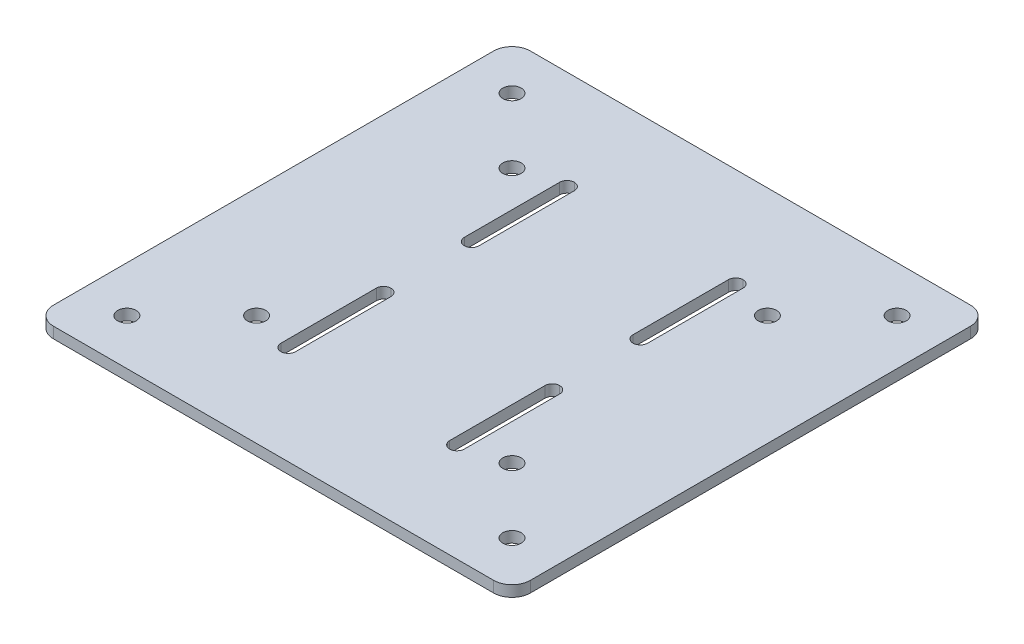
SolidWorks part; units mm, degrees
ref_plane "Front Plane" through (0, 0, 0) normal (0, 0, 1) x (1, 0, 0)
ref_plane "Top Plane" through (0, 0, 0) normal (0, 1, 0) x (1, 0, 0)
ref_plane "Right Plane" through (0, 0, 0) normal (1, 0, 0) x (0, 0, -1)
sketch "Sketch1" plane through (0, 0, 0) normal (0, 1, 0) x (1, 0, 0)
  line L0 (-52.5, 52.5) -> (52.5, 52.5) construction
  line L1 (-65, 65) -> (65, 65)
  line L2 (-65, 65) -> (-65, -65)
  line L3 (-65, -65) -> (65, -65)
  line L4 (65, 65) -> (65, -65)
  line L5 (-65, 65) -> (65, -65) construction
  line L6 (-65, -65) -> (65, 65) construction
  line L7 (-99.0677, 0) -> (99.0677, 0) construction
  line L9 (-25, 40) -> (-21, 40)
  line L10 (-25, 40) -> (25, 40) construction
  line L11 (-25, 40) -> (-25, -40) construction
  line L12 (-25, -40) -> (25, -40) construction
  line L13 (25, 40) -> (25, -40) construction
  line L14 (-25, 40) -> (25, -40) construction
  line L15 (-25, -40) -> (25, 40) construction
  line L16 (-25, 40) -> (-25, 10)
  line L17 (-25, 10) -> (-21, 10)
  line L18 (-21, 40) -> (-21, 10)
  line L19 (-25, 40) -> (-21, 10) construction
  line L20 (-25, 10) -> (-21, 40) construction
  line L21 (25, 40) -> (21, 40)
  line L22 (25, 40) -> (25, 10)
  line L23 (25, 10) -> (21, 10)
  line L24 (21, 40) -> (21, 10)
  line L25 (25, 40) -> (21, 10) construction
  line L26 (25, 10) -> (21, 40) construction
  line L27 (25, -40) -> (21, -40)
  line L28 (25, -40) -> (25, -10)
  line L29 (25, -10) -> (21, -10)
  line L30 (21, -40) -> (21, -10)
  line L31 (25, -40) -> (21, -10) construction
  line L32 (25, -10) -> (21, -40) construction
  line L33 (-25, -40) -> (-21, -40)
  line L34 (-25, -40) -> (-25, -10)
  line L35 (-25, -10) -> (-21, -10)
  line L36 (-21, -40) -> (-21, -10)
  line L37 (-25, -40) -> (-21, -10) construction
  line L38 (-25, -10) -> (-21, -40) construction
  circle A0 centre (-52.5, 52.5) radius 2.5
  circle A1 centre (-34.8223, 34.8223) radius 2.5
  circle A2 centre (52.5, 52.5) radius 2.5
  circle A3 centre (34.8223, 34.8223) radius 2.5
  circle A4 centre (52.5, -52.5) radius 2.5
  circle A5 centre (34.8223, -34.8223) radius 2.5
  circle A6 centre (-34.8223, -34.8223) radius 2.5
  circle A7 centre (-52.5, -52.5) radius 2.5
  point P0 (0, 0)
  point P17 (0, 0)
  point P28 (-23, 25)
  point P32 (23, 25)
  point P33 (0, 0)
  point P41 (23, -25)
  point P45 (-23, -25)
  dimension "D3" = 5
  dimension "D6" = 80
  dimension "D7" = 50
  dimension "D1" = 130
  dimension "D2" = 25
  dimension "D4" = 25
  dimension "D5" = 105
  dimension "D8" = 30
  dimension "D9" = 4
extrude "Boss-Extrude1" add sketch "Sketch1" along normal blind 3
fillet "Fillet1" radius 5 4 edges at (-65, 1.5, 65) (65, 1.5, 65) (65, 1.5, -65) (-65, 1.5, -65)
fillet "Fillet2" radius 2 16 edges at (-25, 1.5, 40) (-21, 1.5, 40) (-25, 1.5, 10) (-21, 1.5, 10) (-21, 1.5, -10) (-25, 1.5, -10) (-25, 1.5, -40) (-21, 1.5, -40) (25, 1.5, -40) (21, 1.5, -40) (21, 1.5, -10) (25, 1.5, -10) (21, 1.5, 10) (25, 1.5, 10) (21, 1.5, 40) (25, 1.5, 40)
